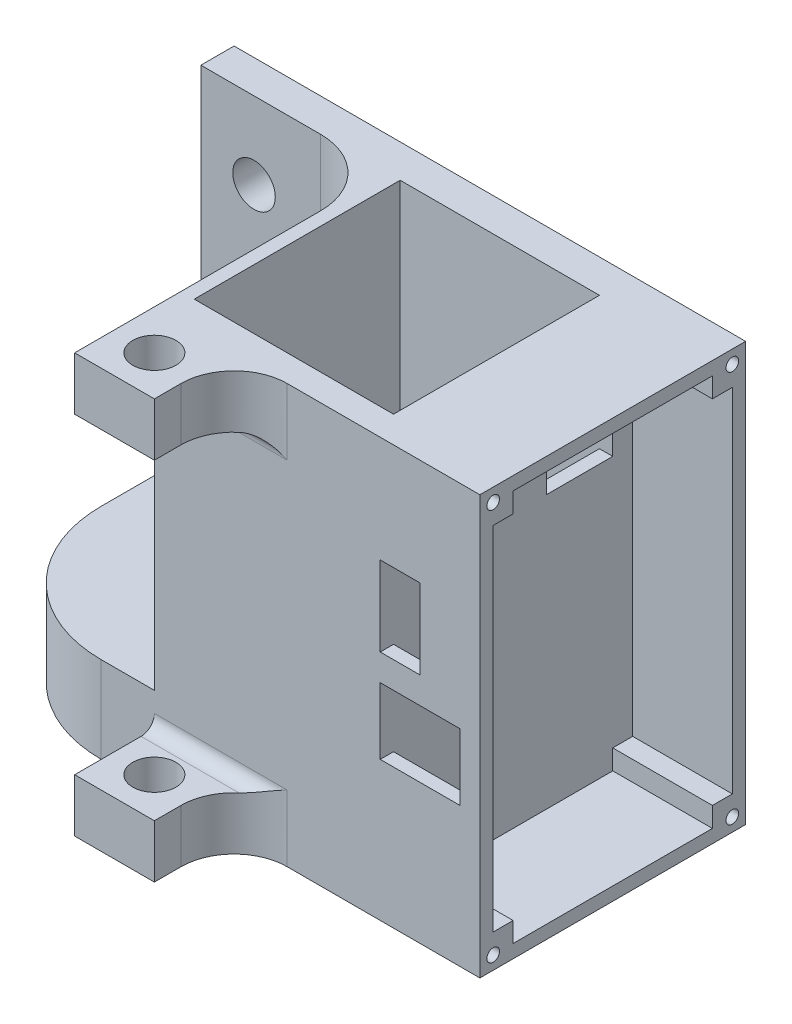
SolidWorks part; units mm, degrees
ref_plane "Front Plane" through (0, 0, 0) normal (0, 0, 1) x (1, 0, 0)
ref_plane "Top Plane" through (0, 0, 0) normal (0, 1, 0) x (1, 0, 0)
ref_plane "Right Plane" through (0, 0, 0) normal (1, 0, 0) x (0, 0, -1)
sketch "Sketch1" plane through (0, 0, 0) normal (0, 1, 0) x (1, 0, 0)
  line L0 (0, 0) -> (80, 0) construction
  line L1 (0, 20) -> (80, 20)
  line L2 (0, -20) -> (80, -20)
  line L3 (42, 20) -> (42, -20)
  line L4 (-20, 0) -> (0, 0)
  line L5 (-20, 0) -> (-20, 20)
  line L6 (-20, 20) -> (0, 20)
  line L7 (0, 0) -> (0, 20)
  circle A0 centre (0, 0) radius 7.11
  arc A1 (0, 20) -> (0, -20) centre (0, 0) ccw
  arc A2 (80, -20) -> (80, 20) centre (80, 0) ccw
  circle A4 centre (25, 0) radius 7.5
  point P3 (40, 0)
  dimension "D1" = 14.22
  dimension "D3" = 25
  dimension "D4" = 15
  dimension "D2" = 80
  dimension "D5" = 42
extrude "Boss-Extrude1" add sketch "Sketch1" along normal blind 5 contours A2 | A2 | A0 L0 A4 L3 L1 L7 | L0 A0 L4 A1 L2 L3 A4 | L7 A1 L4 A0 | A1 L6 L5 region at (21.5064, 0, -11.2354) region at (12.9405, 0, 10.6913) region at (-9.2797, 0, -9.2797) region at (-15.5326, 0, -15.5326)
sketch "Sketch2" plane through (0, 5, 0) normal (0, 1, 0) x (1, 0, 0)
  line L0 (-20, 20) -> (42, 20) construction
  line L1 (10, 20) -> (40, 20)
  line L2 (10, 20) -> (10, -20)
  line L3 (10, -20) -> (40, -20)
  line L4 (40, 20) -> (40, -20)
  line L5 (0, -20) -> (42, -20) construction
  circle A0 centre (25, 0) radius 12.5209
  dimension "D1" = 30
  dimension "D2" = 10
extrude "Boss-Extrude2" add sketch "Sketch2" along normal blind 8
sketch "Sketch3" plane through (0, 0, 0) normal (0, -1, 0) x (1, 0, 0)
  line L1 (13.5, -11.5) -> (36.5, -11.5) construction
  line L2 (13.5, -11.5) -> (13.5, 11.5) construction
  line L3 (13.5, 11.5) -> (36.5, 11.5) construction
  line L4 (36.5, -11.5) -> (36.5, 11.5) construction
  line L5 (13.5, -11.5) -> (36.5, 11.5) construction
  line L6 (13.5, 11.5) -> (36.5, -11.5) construction
  circle A0 centre (13.5, 11.5) radius 1.5
  circle A1 centre (36.5, 11.5) radius 1.5
  circle A2 centre (13.5, -11.5) radius 1.6909
  circle A3 centre (36.5, -11.5) radius 1.5
  point P0 (25, 0)
  dimension "D1" = 23
  dimension "D2" = 23
extrude "Cut-Extrude1" cut sketch "Sketch3" against normal through all
sketch "Sketch4" plane through (0, 0, 0) normal (0, -1, 0) x (1, 0, 0)
  circle A0 centre (13.5, 11.5) radius 3
  circle A1 centre (36.5, 11.5) radius 3
  circle A2 centre (36.5, -11.5) radius 3
  circle A3 centre (13.5, -11.5) radius 3
extrude "Cut-Extrude2" cut sketch "Sketch4" against normal blind 4
sketch "Sketch5" plane through (0, 0, 0) normal (0, 1, 0) x (1, 0, 0)
  line L1 (-20, 20) -> (42, 20)
  line L2 (-20, 20) -> (-20, 15)
  line L3 (-20, 15) -> (42, 15)
  line L4 (42, 20) -> (42, 15)
  line L5 (40, 20) -> (42, 20) construction
  line L6 (42, 20) -> (42, -20) construction
  line L7 (40, -20) -> (40, 20) construction
  line L8 (10, -20) -> (40, -20)
  line L9 (10, -20) -> (10, -16)
  line L10 (10, -16) -> (40, -16)
  line L11 (40, -20) -> (40, -16)
  dimension "D1" = 5
  dimension "D2" = 4
extrude "Boss-Extrude3" add sketch "Sketch5" along normal blind 55
sketch "Sketch6" plane through (0, 55, 0) normal (0, 1, 0) x (1, 0, 0)
  line L0 (10, 15) -> (10, -16) construction
  line L1 (-20, 20) -> (10, 20)
  line L2 (-20, 20) -> (-20, 0)
  line L3 (-20, 0) -> (10, 0)
  line L4 (10, 20) -> (10, 0)
  line L6 (10, 0) -> (0, 0)
  line L7 (10, 0) -> (10, -20)
  line L8 (10, -20) -> (0, -20)
  line L9 (0, 0) -> (0, -20)
  circle A0 centre (0, 0) radius 20
  point P12 (-20, 20)
  line M6 (-20, 20) -> (-20, 15)
  line M7 (-20, 15) -> (42, 15)
  line M9 (42, 20) -> (-20, 20)
extrude "Boss-Extrude4" add sketch "Sketch6" against normal blind 5 contours A0 L1 M6 M7 | A0 L2 M7 | L4 A0 M7 | A0 L4 M9 | A0 L3 L4 M7 | L9 A0 L7 L3 | A0 L8 L7 | L3 A0 L9 region at (-14.1001, 55, -17.8954) region at (7.5347, 55, -19.2063) region at (-0.5141, 55, -17.0796) region at (-18.0451, 55, -11.3888) region at (-4.0291, 55, -7.2106) region at (-8.4883, 55, 8.4883) region at (4.885, 55, 9.5824) region at (7.5347, 55, 19.2063)
sketch "Sketch7" plane through (0, 5, 0) normal (0, 1, 0) x (1, 0, 0)
  line L0 (40, -20) -> (0, -20) construction
  line L1 (10, 15) -> (8, 15)
  line L2 (10, 15) -> (10, -20)
  line L3 (10, -20) -> (8, -20)
  line L4 (8, 15) -> (8, -20)
  line L5 (40, -20) -> (40, 15) construction
  line L6 (40, 15) -> (42, 15)
  line L7 (40, 15) -> (40, -20)
  line L8 (40, -20) -> (42, -20)
  line L9 (42, 15) -> (42, -20)
  line L10 (10, 15) -> (42, 15) construction
  point P15 (42, -20)
  dimension "D1" = 2
  dimension "D2" = 2
extrude "Boss-Extrude5" add sketch "Sketch7" along normal blind 50
sketch "Sketch8" plane through (0, 0, -15) normal (0, 0, 1) x (1, 0, 0)
  line L0 (8, 5) -> (-20, 5) construction
  line L1 (-20, 50) -> (-20, 5) construction
  circle A0 centre (-12, 18) radius 3.2
  circle A1 centre (-12, 43.4) radius 3.2
  point P4 (-10.8697, 18.8254)
  dimension "D1" = 25.4
  dimension "D2" = 13
  dimension "D3" = 8
extrude "Cut-Extrude3" cut sketch "Sketch8" against normal blind 50
sketch "Sketch9" plane through (0, 0, 0) normal (0, -1, 0) x (1, 0, 0)
  line L0 (0, 20) -> (42, 20) construction
  line L1 (25, 20) -> (42, 20)
  line L2 (25, 20) -> (25, -20)
  line L3 (25, -20) -> (42, -20)
  line L4 (42, 20) -> (42, -20)
  line L5 (25, 20) -> (0, 20)
  circle A0 centre (0, 0) radius 20
  circle A1 centre (25, 0) radius 12
  circle A2 centre (0, 0) radius 18
  circle A3 centre (25, 0) radius 10
  line M3 (-20, -20) -> (42, -20)
  line M6 (42, -20) -> (42, 20)
  line M7 (42, 20) -> (0, 20)
  arc M8 (0, 20) -> (-20, 0) centre (0, 0) ccw
  line M9 (-20, 0) -> (-20, -20)
  circle M12 centre (13.5, 11.5) radius 3
  circle M13 centre (36.5, 11.5) radius 3
  circle M14 centre (36.5, -11.5) radius 3
  circle M15 centre (13.5, -11.5) radius 3
extrude "Boss-Extrude6" add sketch "Sketch9" along normal blind 8 contours A2 A0 M12 M8 M15 | A2 A1 A0 M12 | A3 L2 A1 A0 | A3 A0 A1 A2 | A3 A2 A1 A0 | A2 A0 A1 M15 | A3 A0 A1 L2 | A3 L2 A1 | A1 L2 M3 M6 M7 M13 M14 | L4 L1 M6 | A0 M9 M3 | A1 L2 A0 M7 M12 region at (33.5, 0, 19.5654) region at (17.7227, 0, 16.2961) region at (33.2955, 0, 8.2955) region at (21.3918, 0, 10.1874) region at (7.2312, 0, 18.0842) region at (16.525, 0, 9.532) region at (17.2938, 0, 7.8055) region at (-15.5326, 0, -15.5326) region at (21.3918, 0, -10.1874) region at (17.2938, 0, -7.8055) region at (16.525, 0, -9.532)
sketch "Sketch10" plane through (42, 0, 0) normal (1, 0, 0) x (0, 0, -1)
  line L1 (-20, 55) -> (20, 55)
  line L2 (-20, 55) -> (-20, -8)
  line L3 (-20, -8) -> (20, -8)
  line L4 (20, 55) -> (20, -8)
  line L5 (-18, 53) -> (18, 53)
  line L6 (-18, 53) -> (-18, -6)
  line L7 (-18, -6) -> (18, -6)
  line L8 (18, 53) -> (18, -6)
  line L9 (-18, 53) -> (-15, 53)
  line L10 (-18, 53) -> (-18, 50)
  line L11 (-18, 50) -> (-15, 50)
  line L12 (-15, 53) -> (-15, 50)
  line L13 (18, 53) -> (15, 53)
  line L14 (18, 53) -> (18, 50)
  line L15 (18, 50) -> (15, 50)
  line L16 (15, 53) -> (15, 50)
  line L17 (-18, -6) -> (-15, -6)
  line L18 (-18, -6) -> (-18, -3)
  line L19 (-18, -3) -> (-15, -3)
  line L20 (-15, -6) -> (-15, -3)
  line L21 (18, -6) -> (15, -6)
  line L22 (18, -6) -> (18, -3)
  line L23 (18, -3) -> (15, -3)
  line L24 (15, -6) -> (15, -3)
  line M9 (20, 55) -> (-20, 55)
  line M10 (-20, 55) -> (-20, -8)
  line M11 (-20, -8) -> (20, -8)
  line M12 (20, -8) -> (20, 55)
  dimension "D1" = 2
  dimension "D2" = 2
  dimension "D3" = 2
  dimension "D4" = 2
  dimension "D5" = 3
  dimension "D6" = 3
  dimension "D7" = 3
  dimension "D8" = 3
  dimension "D9" = 3
  dimension "D10" = 3
  dimension "D11" = 3
  dimension "D12" = 3
extrude "Boss-Extrude7" add sketch "Sketch10" along normal blind 15 contours L5 L8 L7 L6 M12 M9 M10 M11 | L12 L5 L6 L11 | L5 L16 L15 L8 | L24 L7 L8 L23 | L7 L20 L19 L6 region at (42, 54.2537, 0) region at (42, 51.5, 16.5) region at (42, 51.5, -16.5) region at (42, -4.5, 16.5) region at (42, -4.5, -16.5)
sketch "Sketch11" plane through (42, 0, 0) normal (1, 0, 0) x (0, 0, -1)
  line L0 (15, 53) -> (-15, 53) construction
  line L1 (15, 50) -> (5, 50)
  line L2 (15, 50) -> (15, 35)
  line L3 (15, 35) -> (5, 35)
  line L4 (5, 50) -> (5, 35)
  line L5 (18, -3) -> (18, 50) construction
  dimension "D1" = 3
  dimension "D2" = 3
  dimension "D3" = 10
  dimension "D4" = 15
extrude "Cut-Extrude4" cut sketch "Sketch11" against normal blind 15
sketch "Sketch12" plane through (0, 0, 20) normal (0, 0, 1) x (1, 0, 0)
  line L1 (42, 39) -> (48, 39)
  line L2 (42, 39) -> (42, 27)
  line L3 (42, 27) -> (48, 27)
  line L4 (48, 39) -> (48, 27)
  line L5 (42, 23) -> (54, 23)
  line L6 (42, 23) -> (42, 13)
  line L7 (42, 13) -> (54, 13)
  line L8 (54, 23) -> (54, 13)
  line L9 (0, 55) -> (57, 55) construction
  line L10 (57, 55) -> (57, -8) construction
  dimension "D1" = 15
  dimension "D2" = 15
  dimension "D3" = 12
  dimension "D4" = 6
  dimension "D5" = 16
  dimension "D6" = 12
  dimension "D7" = 32
  dimension "D8" = 10
extrude "Cut-Extrude5" cut sketch "Sketch12" against normal blind 15
sketch "Sketch13" plane through (57, 0, 0) normal (1, 0, 0) x (0, 0, -1)
  line L0 (20, 55) -> (-20, 55) construction
  line L1 (-20, 55) -> (-20, -8) construction
  line L2 (20, -8) -> (20, 55) construction
  line L3 (-20, -8) -> (20, -8) construction
  circle A0 centre (-18, 53) radius 0.95
  circle A1 centre (18, 53) radius 0.95
  circle A2 centre (-18, -6) radius 0.95
  circle A3 centre (18, -6) radius 0.95
  dimension "D1" = 2
  dimension "D3" = 2
  dimension "D5" = 2
  dimension "D2" = 2
  dimension "D4" = 2
extrude "Cut-Extrude6" cut sketch "Sketch13" against normal blind 15
sketch "Sketch14" plane through (0, 55, 0) normal (0, 1, 0) x (1, 0, 0)
  line L0 (10, 15) -> (10, -16) construction
  line L1 (8, 15) -> (-24.4755, 15)
  line L2 (8, 15) -> (8, -23.9264)
  line L3 (8, -23.9264) -> (-24.4755, -23.9264)
  line L4 (-24.4755, 15) -> (-24.4755, -23.9264)
  line L5 (57, 20) -> (-20, 20) construction
  dimension "D1" = 2
  dimension "D2" = 5
extrude "Cut-Extrude7" cut sketch "Sketch14" against normal blind 15
sketch "Sketch15" plane through (0, 0, 0) normal (0, 1, 0) x (1, 0, 0)
  line L1 (8, -20) -> (20, -20)
  line L2 (8, -20) -> (8, -32)
  line L3 (8, -32) -> (20, -32)
  line L4 (20, -20) -> (20, -32)
  circle A0 centre (14, -26) radius 3.25
  point P7 (13.8325, -27.641)
  dimension "D3" = 6.5
  dimension "D1" = 12
  dimension "D2" = 12
  dimension "D4" = 6
  dimension "D5" = 6
extrude "Boss-Extrude8" add sketch "Sketch15" against normal blind 8
pattern_linear "LPattern1" count 2 spacing 55 along (0, 1, 0) of "Boss-Extrude8"
fillet "Fillet1" radius 10 1 edges at (8, 30, -15)
fillet "Fillet2" radius 2 2 edges at (14, 0, 20) (14, 47, 20)
fillet "Fillet3" radius 8 2 edges at (20, -3, 20) (20, 50, 20)
